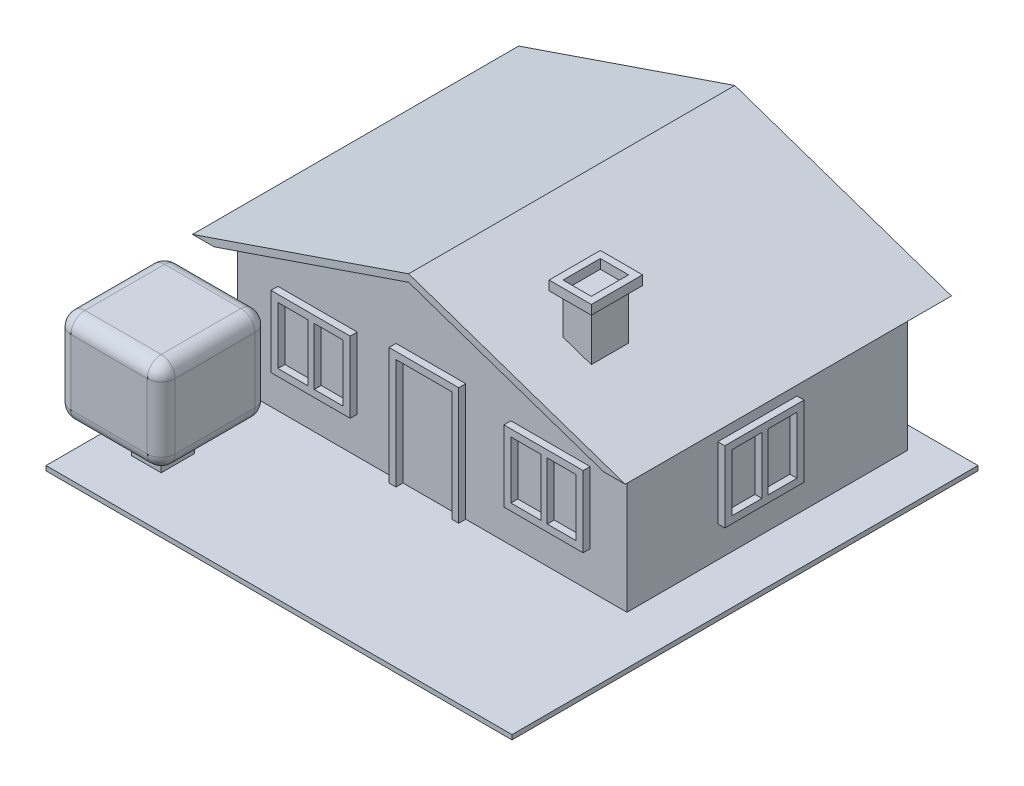
SolidWorks part; units mm, degrees
ref_plane "Plano frontal" through (0, 0, 0) normal (0, 0, 1) x (1, 0, 0)
ref_plane "Plano superior" through (0, 0, 0) normal (0, 1, 0) x (1, 0, 0)
ref_plane "Plano direito" through (0, 0, 0) normal (1, 0, 0) x (0, 0, -1)
sketch "Esboço1" plane through (0, 0, 0) normal (0, 1, 0) x (1, 0, 0)
  line L1 (-0.5, -0.5) -> (0.5, -0.5)
  line L2 (-0.5, -0.5) -> (-0.5, 0.5)
  line L3 (-0.5, 0.5) -> (0.5, 0.5)
  line L4 (0.5, -0.5) -> (0.5, 0.5)
  line L5 (-0.5, -0.5) -> (0.5, 0.5) construction
  line L6 (-0.5, 0.5) -> (0.5, -0.5) construction
  point P0 (0, 0)
  dimension "D1" = 1
  dimension "D2" = 1
extrude "Ressalto-extrusão1" add sketch "Esboço1" along normal blind 0.01
sketch "Esboço2" plane through (0, 0.01, 0) normal (0, 1, 0) x (1, 0, 0)
  line L1 (0.3962, 0.4525) -> (-0.4397, 0.4525)
  line L2 (0.3962, 0.4525) -> (0.3962, -0.1494)
  line L3 (0.3962, -0.1494) -> (-0.4397, -0.1494)
  line L4 (-0.4397, 0.4525) -> (-0.4397, -0.1494)
  line L5 (0.3962, 0.4525) -> (-0.4397, -0.1494) construction
  line L6 (0.3962, -0.1494) -> (-0.4397, 0.4525) construction
  point P0 (-0.0218, 0.1515)
extrude "Ressalto-extrusão3" add sketch "Esboço2" along normal blind 0.3
sketch "Esboço3" plane through (0, 0, 0) normal (0, 0, 1) x (1, 0, 0)
  line L3 (-0.0218, 0.31) -> (-0.0218, 0.4555) construction
  line L4 (-0.4397, 0.31) -> (0.3962, 0.31) construction
  line L5 (-0.0218, 0.4555) -> (-0.4857, 0.2968)
  line L6 (-0.4857, 0.2968) -> (0.4431, 0.2968)
  line L7 (0.4431, 0.2968) -> (-0.0218, 0.4555)
extrude "Ressalto-extrusão5" add sketch "Esboço3" along normal blind 0.2 and the other way blind 0.5
sketch "Esboço4" plane through (0, 0, 0.2) normal (0, 0, 1) x (1, 0, 0)
  line L0 (-0.4394, 0.2968) -> (0.3967, 0.2968)
  line L26 (0.4382, 0.2826) -> (-0.0218, 0.4396)
  line L27 (-0.0218, 0.4396) -> (-0.4808, 0.2826)
  line L28 (0.3967, 0.2968) -> (-0.0218, 0.4396)
  line L29 (-0.0218, 0.4396) -> (-0.4394, 0.2968)
  dimension "D1" = 0.015
extrude "Corte-extrusão2" cut sketch "Esboço4" against normal up to surface (0.0506 mm away) up to face at (-0.0218, 0.1534, 0.1494)
sketch "Esboço5" plane through (0, 0, -0.5) normal (0, 0, -1) x (-1, 0, 0)
  line L0 (0.4712, 0.2859) -> (-0.4234, 0.2876)
  line L5 (0.0218, 0.4396) -> (0.4808, 0.2826)
  line L6 (-0.4382, 0.2826) -> (0.0218, 0.4396)
  line L7 (0.0218, 0.4396) -> (0.4712, 0.2859)
  line L8 (-0.4234, 0.2876) -> (0.0218, 0.4396)
  dimension "D1" = 0.015
extrude "Corte-extrusão5" cut sketch "Esboço5" against normal up to surface (0.0475 mm away) up to face at (-0.0218, 0.1534, -0.4525)
sketch "Esboço6" plane through (0, 0, 0.1494) normal (0, 0, 1) x (1, 0, 0)
  line L1 (-0.0845, 0.01) -> (0.0351, 0.01)
  line L2 (-0.0845, 0.01) -> (-0.0845, 0.2469)
  line L3 (-0.0845, 0.2469) -> (0.0351, 0.2469)
  line L4 (0.0351, 0.01) -> (0.0351, 0.2469)
  line L7 (-0.4397, 0.01) -> (0.3962, 0.01) construction
  line L8 (-0.0995, 0.01) -> (-0.0995, 0.2619)
  line L9 (-0.0995, 0.2619) -> (0.0501, 0.2619)
  line L10 (0.0501, 0.01) -> (0.0501, 0.2619)
  line L11 (-0.3529, 0.2414) -> (-0.1829, 0.2414)
  line L12 (-0.3379, 0.2264) -> (-0.2731, 0.2264)
  line L13 (-0.3379, 0.2264) -> (-0.3379, 0.1036)
  line L14 (-0.3379, 0.1036) -> (-0.2731, 0.1036)
  line L15 (-0.1979, 0.2264) -> (-0.1979, 0.1036)
  line L20 (-0.1829, 0.2414) -> (-0.1829, 0.0886)
  line L21 (-0.3529, 0.0886) -> (-0.1829, 0.0886)
  line L22 (-0.3529, 0.2414) -> (-0.3529, 0.0886)
  line L27 (-0.2731, 0.2264) -> (-0.2731, 0.1036)
  line L28 (-0.26, 0.2264) -> (-0.26, 0.1036)
  line L29 (-0.26, 0.2264) -> (-0.1979, 0.2264)
  line L30 (-0.3379, 0.2264) -> (-0.1979, 0.2264) construction
  line L31 (-0.26, 0.1036) -> (-0.1979, 0.1036)
  line L32 (-0.3379, 0.1036) -> (-0.1979, 0.1036) construction
  line L33 (0.1471, 0.2414) -> (0.3171, 0.2414)
  line L34 (0.1621, 0.2264) -> (0.2269, 0.2264)
  line L35 (0.1621, 0.2264) -> (0.1621, 0.1036)
  line L36 (0.1621, 0.1036) -> (0.2269, 0.1036)
  line L37 (0.3021, 0.2264) -> (0.3021, 0.1036)
  line L38 (0.3171, 0.2414) -> (0.3171, 0.0886)
  line L39 (0.1471, 0.0886) -> (0.3171, 0.0886)
  line L40 (0.1471, 0.2414) -> (0.1471, 0.0886)
  line L41 (0.2269, 0.2264) -> (0.2269, 0.1036)
  line L42 (0.24, 0.2264) -> (0.24, 0.1036)
  line L43 (0.24, 0.2264) -> (0.3021, 0.2264)
  line L44 (0.24, 0.1036) -> (0.3021, 0.1036)
  line M42 (-0.4397, 0.01) -> (0.3962, 0.01)
  dimension "D2" = 0.14
  dimension "D3" = 2
  dimension "D1" = 0.015
  dimension "D4" = 0.015
sketch "Esboço7" plane through (-0.4397, 0, 0) normal (-1, 0, 0) x (0, 0, 1)
  line L0 (-0.2432, 0.2339) -> (-0.0732, 0.2339)
  line L1 (-0.2282, 0.2189) -> (-0.1634, 0.2189)
  line L2 (-0.2282, 0.2189) -> (-0.2282, 0.0961)
  line L3 (-0.2282, 0.0961) -> (-0.1634, 0.0961)
  line L4 (-0.0882, 0.2189) -> (-0.0882, 0.0961)
  line L5 (-0.0732, 0.2339) -> (-0.0732, 0.0811)
  line L6 (-0.2432, 0.0811) -> (-0.0732, 0.0811)
  line L7 (-0.2432, 0.2339) -> (-0.2432, 0.0811)
  line L8 (-0.1634, 0.2189) -> (-0.1634, 0.0961)
  line L9 (-0.1502, 0.2189) -> (-0.1502, 0.0961)
  line L10 (-0.1502, 0.2189) -> (-0.0882, 0.2189)
  line L11 (-0.1502, 0.0961) -> (-0.0882, 0.0961)
  dimension "D1" = 0.14
sketch "Esboço8" plane through (0.3962, 0, 0) normal (1, 0, 0) x (0, 0, -1)
  line L0 (0.0455, 0.2296) -> (0.2155, 0.2296)
  line L1 (0.0605, 0.2146) -> (0.1252, 0.2146)
  line L2 (0.0605, 0.2146) -> (0.0605, 0.0918)
  line L3 (0.0605, 0.0918) -> (0.1252, 0.0918)
  line L4 (0.2005, 0.2146) -> (0.2005, 0.0918)
  line L5 (0.2155, 0.2296) -> (0.2155, 0.0768)
  line L6 (0.0455, 0.0768) -> (0.2155, 0.0768)
  line L7 (0.0455, 0.2296) -> (0.0455, 0.0768)
  line L8 (0.1252, 0.2146) -> (0.1252, 0.0918)
  line L9 (0.1384, 0.2146) -> (0.1384, 0.0918)
  line L10 (0.1384, 0.2146) -> (0.2005, 0.2146)
  line L11 (0.1384, 0.0918) -> (0.2005, 0.0918)
  dimension "D1" = 0.14
extrude "Ressalto-extrusão7" add sketch "Esboço8" along normal blind 0.015
extrude "Ressalto-extrusão8" add sketch "Esboço7" along normal blind 0.015
extrude "Ressalto-extrusão9" add sketch "Esboço6" along normal blind 0.015 contours L10 L9 L8 L2 L3 L4 M42 | L11 L22 L21 L20 L31 L28 L29 L15 L12 L27 L14 L13 | L33 L40 L39 L38 L44 L42 L43 L37 L34 L41 L36 L35 region at (-0.092, 0.0129, 0.1494) region at (-0.2677, 0.165, 0.1494) region at (0.2323, 0.165, 0.1494)
sketch "Esboço9" plane through (0, 0.01, 0) normal (0, 1, 0) x (1, 0, 0)
  line L1 (-0.4267, -0.3189) -> (-0.3629, -0.3189)
  line L2 (-0.4267, -0.3189) -> (-0.4267, -0.3899)
  line L3 (-0.4267, -0.3899) -> (-0.3629, -0.3899)
  line L4 (-0.3629, -0.3189) -> (-0.3629, -0.3899)
extrude "Ressalto-extrusão10" add sketch "Esboço9" along normal blind 0.07
sketch "Esboço11" plane through (0, 0.08, 0) normal (0, 1, 0) x (1, 0, 0)
  line L18 (-0.5067, -0.2389) -> (-0.5067, -0.4699)
  line L19 (-0.5067, -0.4699) -> (-0.2829, -0.4699)
  line L20 (-0.2829, -0.4699) -> (-0.2829, -0.2389)
  line L21 (-0.2829, -0.2389) -> (-0.5067, -0.2389)
  line L22 (-0.5067, -0.2389) -> (-0.5067, -0.4699)
  line L23 (-0.5067, -0.4699) -> (-0.2829, -0.4699)
  line L24 (-0.2829, -0.4699) -> (-0.2829, -0.2389)
  line L25 (-0.2829, -0.2389) -> (-0.5067, -0.2389)
  dimension "D1" = 0.08
extrude "Ressalto-extrusão11" add sketch "Esboço11" along normal blind 0.2
fillet "Filete2" radius 0.03 9 edges at (-0.2829, 0.18, 0.4699) (-0.3948, 0.08, 0.4699) (-0.2829, 0.28, 0.3544) (-0.3948, 0.28, 0.4699) (-0.3948, 0.28, 0.2389) (-0.5067, 0.18, 0.2389) (-0.5067, 0.28, 0.3544) (-0.5067, 0.18, 0.4699) (-0.5067, 0.08, 0.3544)
fillet "Filete3" radius 0.03 6 edges at (-0.4979, 0.0888, 0.2477) (-0.2916, 0.2712, 0.2477) (-0.2916, 0.0888, 0.4611) (-0.3798, 0.08, 0.2389) (-0.2829, 0.165, 0.2389) (-0.2829, 0.08, 0.3394)
sketch "Esboço12" plane through (0, 0, 0) normal (0, 0, 1) x (1, 0, 0)
  line L0 (0.1895, 0.3833) -> (0.2502, 0.3626)
  line L1 (0.4431, 0.2968) -> (-0.0218, 0.4555) construction
  line L2 (0.2502, 0.3626) -> (0.2502, 0.4695)
  line L3 (0.2502, 0.4695) -> (0.1895, 0.4695)
  line L4 (0.1895, 0.4695) -> (0.1895, 0.3833)
extrude "Ressalto-extrusão12" add sketch "Esboço12" along normal blind 0.08
sketch "Esboço13" plane through (0, 0.4695, 0) normal (0, 1, 0) x (1, 0, 0)
  line L10 (0.2502, 0) -> (0.1895, 0) construction
  line L11 (0.1895, -0.08) -> (0.1895, 0) construction
  line L12 (0.2502, -0.08) -> (0.1895, -0.08) construction
  line L13 (0.2502, -0.08) -> (0.2502, 0) construction
  line L14 (0.2652, 0.015) -> (0.1745, 0.015)
  line L15 (0.1745, 0.015) -> (0.1745, -0.095)
  line L16 (0.1745, -0.095) -> (0.2652, -0.095)
  line L17 (0.2652, -0.095) -> (0.2652, 0.015)
  line L18 (0.2652, 0.015) -> (0.1745, 0.015)
  line L19 (0.1745, 0.015) -> (0.1745, -0.095)
  line L20 (0.1745, -0.095) -> (0.2652, -0.095)
  line L21 (0.2652, -0.095) -> (0.2652, 0.015)
  line L22 (0.2502, 0) -> (0.1895, 0)
  line L23 (0.1895, -0.08) -> (0.1895, 0)
  line L24 (0.2502, -0.08) -> (0.1895, -0.08)
  line L25 (0.2502, -0.08) -> (0.2502, 0)
  dimension "D1" = 0.015
extrude "Ressalto-extrusão13" add sketch "Esboço13" along normal blind 0.02 separate body
